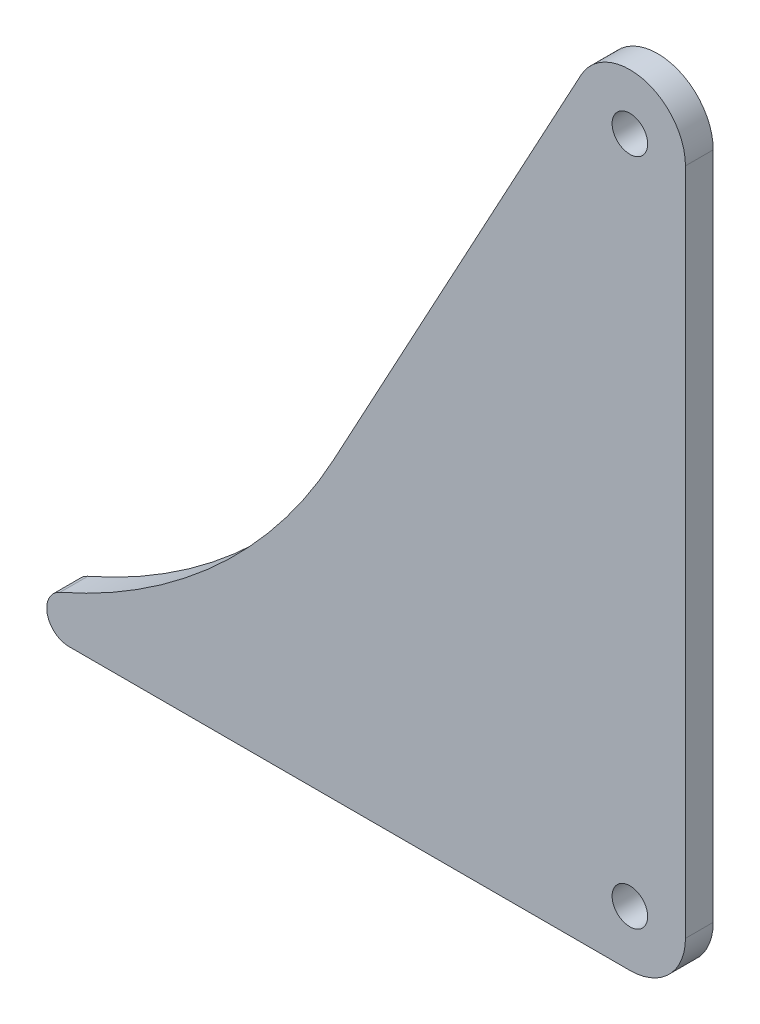
SolidWorks part; units mm, degrees
ref_plane "Front Plane" through (0, 0, 0) normal (0, 0, 1) x (1, 0, 0)
ref_plane "Top Plane" through (0, 0, 0) normal (0, 1, 0) x (1, 0, 0)
ref_plane "Right Plane" through (0, 0, 0) normal (1, 0, 0) x (0, 0, -1)
sketch "Sketch1" plane through (0, 0, 0) normal (0, 0, 1) x (1, 0, 0)
  line L0 (0, 0) -> (0, 107.8625)
  line L1 (0, 0) -> (-88.9, 0)
  line L2 (0, 107.8625) -> (-40.2362, 33.5563)
  line L4 (130.3819, 348.6446) -> (-17.145, 76.2) construction
  arc A0 (-88.9, 0) -> (-40.2362, 33.5563) centre (-97.5307, 64.5809) ccw
  dimension "D2" = 88.9
extrude "Boss-Extrude1" add sketch "Sketch1" along normal blind 3.175
fillet "Fillet1" radius 2.54 1 edges at (-88.9, 0, 1.5875)
fillet "Fillet2" radius 6.35 2 edges at (0, 0, 1.5875) (0, 107.8625, 1.5875)
sketch "Sketch2" plane through (0, 0, 3.175) normal (0, 0, 1) x (1, 0, 0)
  circle A0 centre (-6.35, 6.35) radius 2.032
  circle A1 centre (-6.35, 82.7999) radius 2.032
  arc A2 (0, 82.7999) -> (-11.9339, 85.8236) centre (-6.35, 82.7999) ccw construction
  arc A3 (-6.35, 0) -> (0, 6.35) centre (-6.35, 6.35) ccw construction
  dimension "D3" = 4.064
extrude "Cut-Extrude1" cut sketch "Sketch2" against normal through all
